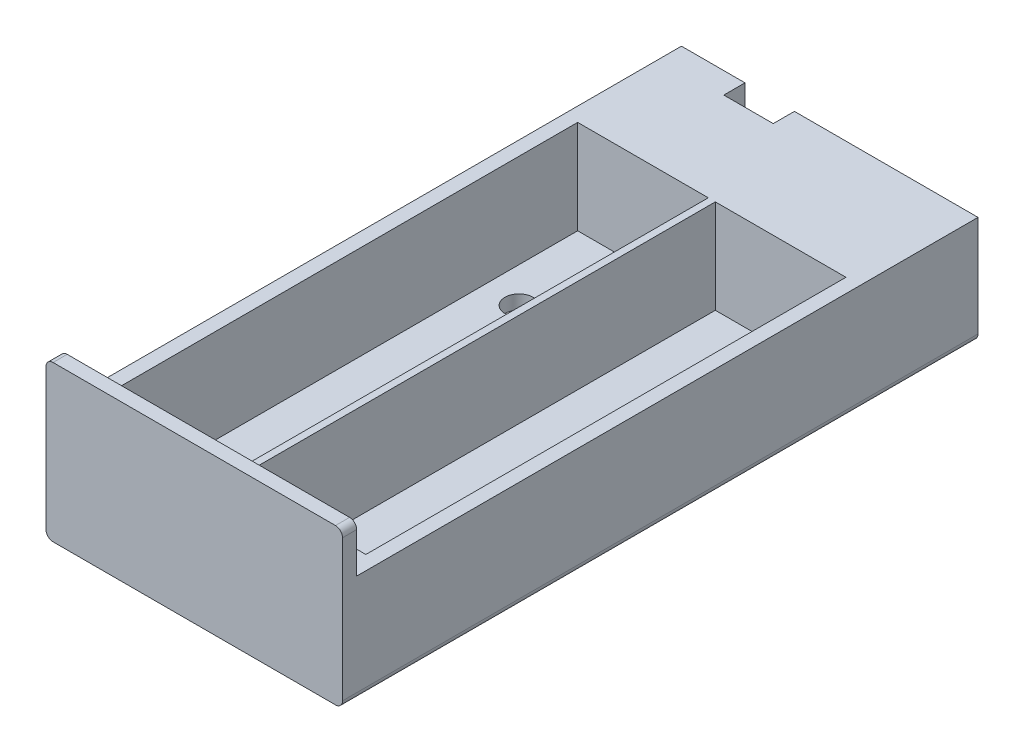
SolidWorks part; units mm, degrees
material "6061 Alloy"
ref_plane "Front" through (0, 0, 0) normal (0, 0, 1) x (1, 0, 0)
ref_plane "Top" through (0, 0, 0) normal (0, 1, 0) x (1, 0, 0)
ref_plane "Right" through (0, 0, 0) normal (1, 0, 0) x (0, 0, -1)
sketch "Sketch1" plane through (0, 0, 0) normal (0, 1, 0) x (1, 0, 0)
  line L1 (-21, -45) -> (21, -45)
  line L2 (-21, -45) -> (-21, 45)
  line L3 (-21, 45) -> (21, 45)
  line L4 (21, -45) -> (21, 45)
  line L5 (-21, -45) -> (21, 45) construction
  line L6 (-21, 45) -> (21, -45) construction
  point P0 (0, 0)
  dimension "D1" = 42
  dimension "D2" = 90
extrude "Boss-Extrude1" add sketch "Sketch1" along normal blind 22
fillet "Fillet1" radius 1 4 edges at (21, 0, 0) (-21, 0, 0) (21, 22, 0) (-21, 22, 0)
sketch "Sketch2" plane through (0, 22, 0) normal (0, 1, 0) x (1, 0, 0)
  line L0 (-20, -45) -> (20, -45) construction
  line L1 (-19, 28.3) -> (19, 28.3)
  line L2 (-19, 28.3) -> (-19, -39.7)
  line L3 (-19, -39.7) -> (19, -39.7)
  line L4 (19, 28.3) -> (19, -39.7)
  line L5 (-19, 28.3) -> (19, -39.7) construction
  line L6 (-19, -39.7) -> (19, 28.3) construction
  point P0 (0, -5.7)
  point P5 (0, 0)
  dimension "D1" = 38
  dimension "D2" = 68
  dimension "D3" = 5.3
extrude "Cut-Extrude1" cut sketch "Sketch2" against normal blind 20 contours L4 L1 L2 L3 region at (0, 22, 5.7)
sketch "Sketch3" plane through (0, 2, 0) normal (0, 1, 0) x (1, 0, 0)
  line L0 (-19, 28.3) -> (19, 28.3) construction
  line L1 (-0.5, 28.3) -> (0.5, 28.3)
  line L2 (-0.5, 28.3) -> (-0.5, -39.7)
  line L3 (-0.5, -39.7) -> (0.5, -39.7)
  line L4 (0.5, 28.3) -> (0.5, -39.7)
  line L5 (-19, -39.7) -> (19, -39.7) construction
  line L6 (0, 28.3) -> (0, -39.7) construction
  dimension "D1" = 1
extrude "Boss-Extrude2" add sketch "Sketch3" along normal up to surface (20 mm away) up to face at (0, 22, 0)
sketch "Sketch4" plane through (0, 22, 0) normal (0, 1, 0) x (1, 0, 0)
  line L0 (21, 45) -> (21, -45) construction
  line L1 (-21, 45) -> (21, 45)
  line L2 (-21, 45) -> (-21, -43)
  line L3 (-21, -43) -> (21, -43)
  line L4 (21, 45) -> (21, -43)
  line L5 (-20, -45) -> (20, -45) construction
  dimension "D1" = 2
extrude "Cut-Extrude2" cut sketch "Sketch4" against normal blind 6.7
sketch "Sketch5" plane through (0, 0, -45) normal (0, 0, -1) x (-1, 0, 0)
  line L0 (-21, 15.3) -> (-21, 1) construction
  line L1 (-20, 0) -> (20, 0) construction
  circle A0 centre (-13.5, 3.5) radius 1.5
  point P4 (-15, 6.9373)
  point P7 (-18.5137, 6.9373)
  point P10 (-11.4863, 3.4236)
  dimension "D3" = 3
  dimension "D1" = 6
  dimension "D2" = 2
extrude "Cut-Extrude3" cut sketch "Sketch5" against normal up to next
sketch "Sketch6" plane through (0, 0, -45) normal (0, 0, -1) x (-1, 0, 0)
  line L0 (-21, 15.3) -> (21, 15.3) construction
  line L1 (12, 15.3) -> (5, 15.3)
  line L2 (12, 15.3) -> (12, 10.3)
  line L3 (12, 10.3) -> (5, 10.3)
  line L4 (5, 15.3) -> (5, 10.3)
  line L5 (21, 15.3) -> (21, 1) construction
  dimension "D1" = 9
  dimension "D2" = 7
  dimension "D3" = 5
extrude "Cut-Extrude4" cut sketch "Sketch6" against normal blind 3
sketch "Sketch7" plane through (0, 0, 0) normal (0, -1, 0) x (1, 0, 0)
  line L0 (-20, 45) -> (20, 45) construction
  line L1 (14, 25) -> (-14, 25) construction
  line L2 (14, 25) -> (14, -15) construction
  line L3 (14, -15) -> (-14, -15) construction
  line L4 (-14, 25) -> (-14, -15) construction
  line L5 (14, 25) -> (-14, -15) construction
  line L6 (14, -15) -> (-14, 25) construction
  circle A0 centre (14, -15) radius 2
  circle A1 centre (14, 25) radius 2
  circle A2 centre (-14, 25) radius 2
  circle A3 centre (-14, -15) radius 2
  point P0 (0, 5)
  point P9 (0, 0)
  dimension "D1" = 4
  dimension "D2" = 28
  dimension "D3" = 40
  dimension "D4" = 20
extrude "Cut-Extrude5" cut sketch "Sketch7" against normal through all
